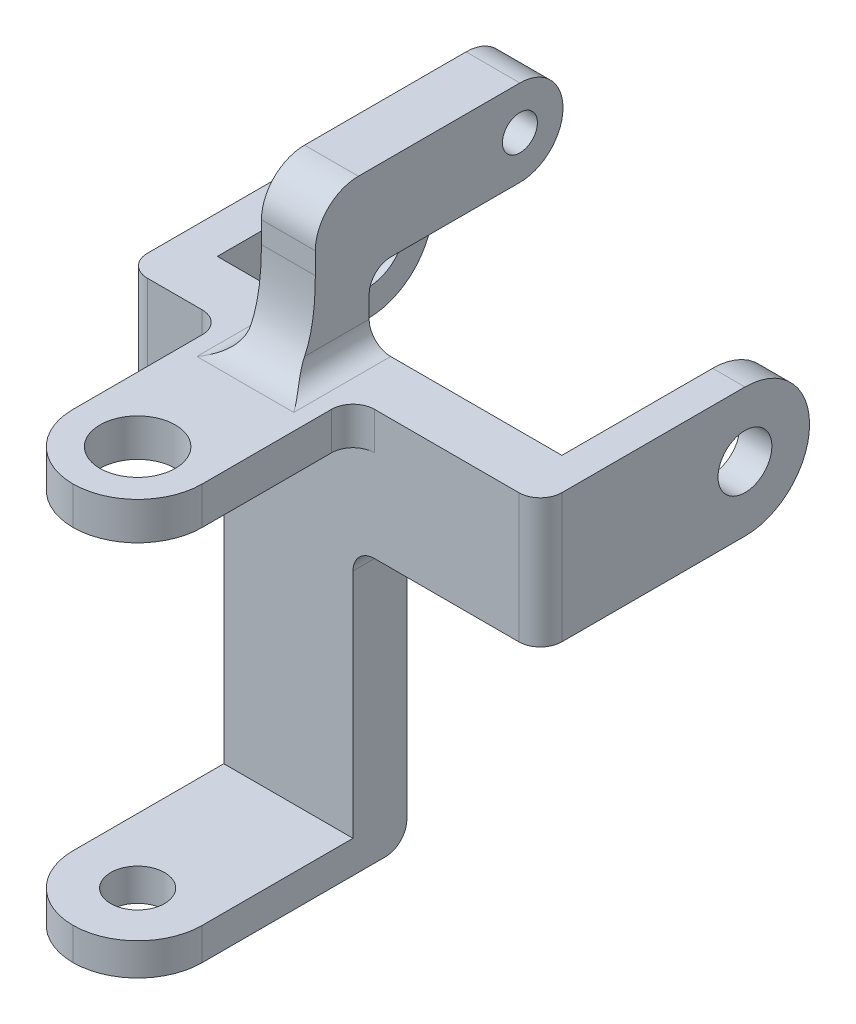
SolidWorks part; units mm, degrees
ref_plane "Front Plane" through (0, 0, 0) normal (0, 0, 1) x (1, 0, 0)
ref_plane "Top Plane" through (0, 0, 0) normal (0, 1, 0) x (1, 0, 0)
ref_plane "Right Plane" through (0, 0, 0) normal (1, 0, 0) x (0, 0, -1)
sketch "Sketch1" plane through (0, 0, 0) normal (0, 0, 1) x (1, 0, 0)
  line L0 (21.1, 0) -> (38.5, 0)
  line L1 (0, 0) -> (9.1, 0)
  line L2 (0, 0) -> (0, 12)
  line L3 (0, 12) -> (12.6, 12)
  line L4 (38.5, 0) -> (38.5, 12)
  line L5 (17.6, 12) -> (38.5, 12)
  line L6 (9.1, 0) -> (9.1, -26.5)
  line L7 (9.1, -26.5) -> (21.1, -26.5)
  line L8 (21.1, 0) -> (21.1, -26.5)
  line L10 (12.6, 12) -> (12.6, 26)
  line L11 (12.6, 26) -> (17.6, 26)
  line L12 (17.6, 12) -> (17.6, 26)
  dimension "D1" = 12
  dimension "D2" = 38.5
  dimension "D3" = 12
  dimension "D4" = 26.5
  dimension "D5" = 9.1
  dimension "D6" = 14
  dimension "D7" = 5
  dimension "D8" = 12.6
extrude "Boss-Extrude1" add sketch "Sketch1" along normal blind 5
sketch "Sketch2" plane through (0, 0, 0) normal (0, 0, -1) x (-1, 0, 0)
  line L0 (-12.6, 12) -> (0, 12) construction
  line L1 (0, 0) -> (-3.5, 0)
  line L2 (0, 0) -> (0, 12)
  line L3 (0, 12) -> (-3.5, 12)
  line L4 (-3.5, 0) -> (-3.5, 12)
  line L5 (-38.5, 12) -> (-17.6, 12) construction
  line L6 (-38.5, 0) -> (-35.5, 0)
  line L7 (-38.5, 0) -> (-38.5, 12)
  line L8 (-38.5, 12) -> (-35.5, 12)
  line L9 (-35.5, 0) -> (-35.5, 12)
  dimension "D1" = 3.5
  dimension "D2" = 3
extrude "Boss-Extrude2" add sketch "Sketch2" along normal blind 20
sketch "Sketch3" plane through (0, 0, 5) normal (0, 0, 1) x (1, 0, 0)
  line L0 (21.1, -26.5) -> (21.1, 0) construction
  line L1 (9.1, -26.5) -> (21.1, -26.5)
  line L2 (9.1, -26.5) -> (9.1, -23.5)
  line L3 (9.1, -23.5) -> (21.1, -23.5)
  line L4 (21.1, -26.5) -> (21.1, -23.5)
  line L5 (12.6, 12) -> (0, 12) construction
  line L6 (9.1, 12) -> (21.1, 12)
  line L7 (9.1, 12) -> (9.1, 8.5)
  line L8 (9.1, 8.5) -> (21.1, 8.5)
  line L9 (21.1, 12) -> (21.1, 8.5)
  line L10 (9.1, 0) -> (9.1, -26.5) construction
  dimension "D1" = 3
  dimension "D2" = 3.5
extrude "Boss-Extrude3" add sketch "Sketch3" along normal blind 20
sketch "Sketch4" plane through (0, 0, 0) normal (0, 0, -1) x (-1, 0, 0)
  line L0 (-12.6, 26) -> (-12.6, 12) construction
  line L1 (-17.6, 26) -> (-12.6, 26)
  line L2 (-17.6, 26) -> (-17.6, 18)
  line L3 (-17.6, 18) -> (-12.6, 18)
  line L4 (-12.6, 26) -> (-12.6, 18)
  dimension "D1" = 8
extrude "Boss-Extrude4" add sketch "Sketch4" along normal blind 18
sketch "Sketch5" plane through (0, 0, 0) normal (-1, 0, 0) x (0, 0, 1)
  line L0 (-20, 0) -> (-20, 12) construction
  line L1 (5, 12) -> (-20, 12) construction
  circle A0 centre (-14, 6) radius 3.5
  dimension "D3" = 7
  dimension "D1" = 6
  dimension "D2" = 6
extrude "Cut-Extrude1" cut sketch "Sketch5" against normal up to surface (3.5 mm away) up to face at (3.5, 7.5, -15)
sketch "Sketch6" plane through (0, 12, 0) normal (0, 1, 0) x (1, 0, 0)
  line L0 (21.1, -25) -> (21.1, -5) construction
  line L1 (21.1, -25) -> (9.1, -25) construction
  circle A0 centre (15.1, -19) radius 3.5
  dimension "D3" = 7
  dimension "D1" = 6
  dimension "D2" = 6
extrude "Cut-Extrude2" cut sketch "Sketch6" against normal up to surface (3.5 mm away) up to face at (15.1, 8.5, 15)
sketch "Sketch7" plane through (12.6, 0, 0) normal (-1, 0, 0) x (0, 0, 1)
  line L0 (-18, 18) -> (-18, 26) construction
  line L1 (5, 26) -> (-18, 26) construction
  circle A0 centre (-14, 22) radius 1.625
  dimension "D3" = 3.25
  dimension "D1" = 4
  dimension "D2" = 4
extrude "Cut-Extrude3" cut sketch "Sketch7" against normal up to surface (5 mm away) up to face at (17.6, 18.6667, -4.3333)
sketch "Sketch8" plane through (35.5, 0, 0) normal (-1, 0, 0) x (0, 0, 1)
  line L0 (-20, 0) -> (-20, 12) construction
  line L1 (-20, 12) -> (0, 12) construction
  circle A0 centre (-14, 6) radius 2.5
  dimension "D3" = 5
  dimension "D1" = 6
  dimension "D2" = 6
extrude "Cut-Extrude4" cut sketch "Sketch8" against normal up to surface (3 mm away) up to face at (38.5, 6, -7.5)
sketch "Sketch9" plane through (0, -23.5, 0) normal (0, 1, 0) x (1, 0, 0)
  line L0 (21.1, -25) -> (9.1, -25) construction
  line L1 (9.1, -25) -> (9.1, -5) construction
  circle A0 centre (15.1, -19) radius 2.5
  dimension "D3" = 5
  dimension "D1" = 6
  dimension "D2" = 6
extrude "Cut-Extrude5" cut sketch "Sketch9" against normal up to surface (3 mm away) up to face at (15.1, -26.5, 12.5)
fillet "Fillet1" radius 6 8 edges at (21.1, -25, 25) (9.1, -25, 25) (37, 0, -20) (37, 12, -20) (21.1, 10.25, 25) (9.1, 10.25, 25) (1.75, 0, -20) (1.75, 12, -20)
fillet "Fillet2" radius 2 4 edges at (15.1, 18, 0) (38.5, 6, 5) (0, 6, 5) (15.1, -26.5, 0)
fillet "Fillet3" radius 2 6 edges at (9.1, 0, 2.5) (21.1, 0, 2.5) (17.6, 12, 2.5) (12.6, 12, 2.5) (21.1, 10.25, 5) (9.1, 10.25, 5)
fillet "Fillet4" radius 4 3 edges at (15.1, 26, 5) (15.1, 26, -18) (15.1, 18, -18)
fillet "Fillet5" radius 8 1 edges at (15.1, 12, 5) second distance 4 first distance on face at (15.1, 15.8619, 5)
